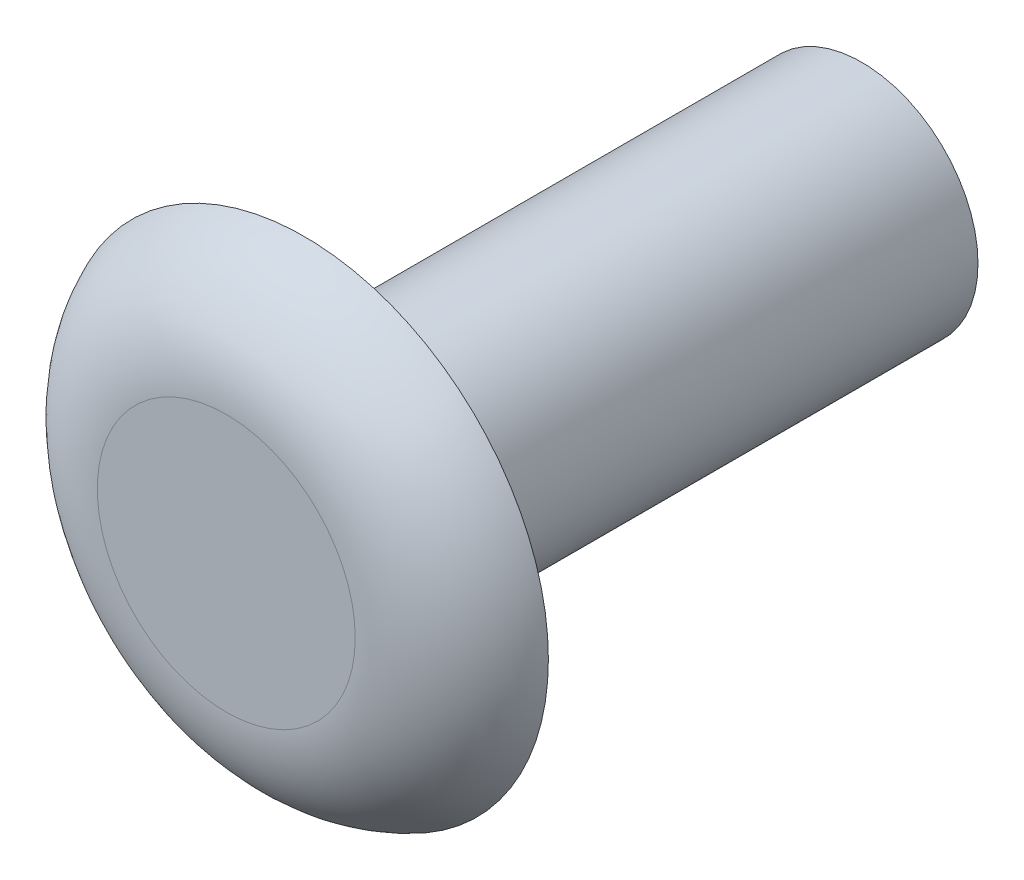
SolidWorks part; units mm, degrees
material "6061 Alloy"
ref_plane "Front Plane" through (0, 0, 0) normal (0, 0, 1) x (1, 0, 0)
ref_plane "Top Plane" through (0, 0, 0) normal (0, 1, 0) x (1, 0, 0)
ref_plane "Right Plane" through (0, 0, 0) normal (1, 0, 0) x (0, 0, -1)
sketch "Sketch1" plane through (0, 0, 0) normal (0, 0, 1) x (1, 0, 0)
  circle A0 centre (0, 0) radius 5.0038
  dimension "D1" = 10.0076
extrude "Boss-Extrude1" add sketch "Sketch1" along normal blind 1.6002
sketch "Sketch2" plane through (0, 0, 0) normal (0, 0, 1) x (1, 0, 0)
  circle A0 centre (0, 0) radius 2.3813
  dimension "D1" = 4.7625
extrude "Boss-Extrude2" add sketch "Sketch2" against normal blind 11.43
fillet "Fillet1" radius 2.54 1 edges at (5.0038, 0, 1.6002)
